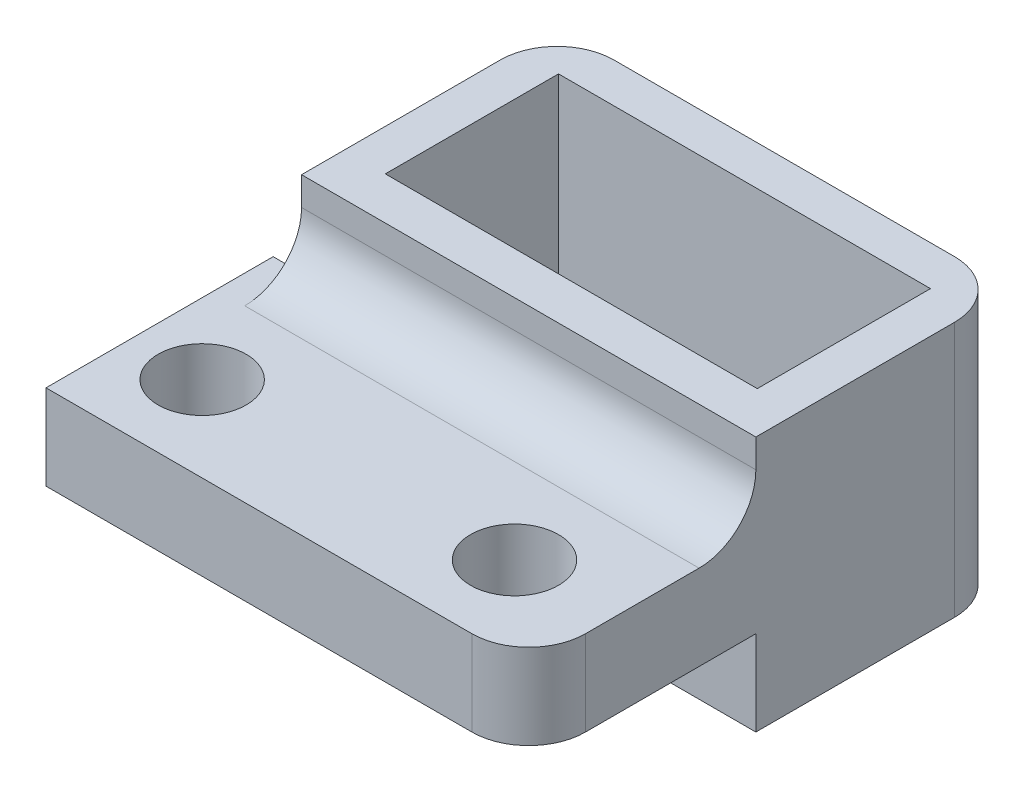
SolidWorks part; units mm, degrees
ref_plane "Alzado" through (0, 0, 0) normal (0, 0, 1) x (1, 0, 0)
ref_plane "Planta" through (0, 0, 0) normal (0, 1, 0) x (1, 0, 0)
ref_plane "Vista lateral" through (0, 0, 0) normal (1, 0, 0) x (0, 0, -1)
sketch "Croquis1" plane through (0, 0, 0) normal (0, 1, 0) x (1, 0, 0)
  line L0 (9, 18) -> (9, 0) construction
  line L1 (0, 0) -> (18, 0)
  line L2 (0, 0) -> (0, 18)
  line L3 (0, 18) -> (18, 18)
  line L4 (18, 0) -> (18, 18)
  circle A0 centre (3.5, 3) radius 1.55
  circle A1 centre (14.5, 3) radius 1.55
  dimension "D3" = 3.1
  dimension "D4" = 3
  dimension "D5" = 3.5
  dimension "D7" = 3
  dimension "D1" = 18
  dimension "D2" = 18
  dimension "D6" = 3.5
extrude "Saliente-Extruir1" add sketch "Croquis1" along normal blind 3
sketch "Croquis3" plane through (0, 3, 0) normal (0, 1, 0) x (1, 0, 0)
  line L0 (18, 0) -> (18, 18) construction
  line L1 (0, 18) -> (18, 18)
  line L2 (0, 18) -> (0, 8)
  line L3 (0, 8) -> (18, 8)
  line L4 (18, 18) -> (18, 8)
  dimension "D1" = 10
extrude "Saliente-Extruir3" add sketch "Croquis3" along normal blind 3
sketch "Croquis4" plane through (0, 0, 0) normal (0, -1, 0) x (1, 0, 0)
  line L1 (0, -18) -> (2, -18)
  line L2 (0, -18) -> (0, -8)
  line L3 (0, -8) -> (2, -8)
  line L4 (2, -18) -> (2, -8)
  dimension "D1" = 10
  dimension "D2" = 2
extrude "Cortar-Extruir1" cut sketch "Croquis4" against normal up to surface (6 mm away) up to face at (9, 6, -13)
sketch "Croquis7" plane through (0, 6, 0) normal (0, 1, 0) x (1, 0, 0)
  line L1 (3.45, 15.6) -> (16.55, 15.6)
  line L2 (3.45, 15.6) -> (3.45, 9.5)
  line L3 (3.45, 9.5) -> (16.55, 9.5)
  line L4 (16.55, 15.6) -> (16.55, 9.5)
  line L5 (2, 8) -> (18, 8) construction
  line L6 (2, 18) -> (2, 8) construction
  dimension "D1" = 6.1
  dimension "D2" = 13.1
  dimension "D3" = 1.5
  dimension "D4" = 1.45
extrude "Cortar-Extruir2" cut sketch "Croquis7" against normal up to surface (6 mm away) up to face at (6.6667, 0, -8.6667)
sketch "Croquis9" plane through (0, 0, 0) normal (0, -1, 0) x (1, 0, 0)
  line L0 (16.55, -15.6) -> (3.45, -15.6) construction
  line L1 (18, -18) -> (2, -18)
  line L2 (18, -18) -> (18, -8)
  line L3 (18, -8) -> (2, -8)
  line L4 (2, -18) -> (2, -8)
  line L5 (3.45, -15.6) -> (3.45, -9.5) construction
  line L6 (3.45, -9.5) -> (16.55, -9.5) construction
  line L7 (16.55, -9.5) -> (16.55, -15.6) construction
  line L8 (3.45, -9.5) -> (16.55, -9.5)
  line L9 (3.45, -15.6) -> (3.45, -9.5)
  line L10 (16.55, -15.6) -> (3.45, -15.6)
  line L11 (16.55, -9.5) -> (16.55, -15.6)
extrude "Saliente-Extruir4" add sketch "Croquis9" along normal blind 3
sketch "Croquis10" plane through (0, -3, 0) normal (0, -1, 0) x (1, 0, 0)
  line L0 (16.55, -15.6) -> (16.55, -9.5) construction
  line L1 (16.55, -9.5) -> (3.45, -9.5) construction
  line L2 (3.45, -9.5) -> (3.45, -15.6) construction
  line L3 (3.45, -15.6) -> (16.55, -15.6) construction
  line L4 (16.55, -15.6) -> (16.55, -9.5)
  line L5 (16.55, -9.5) -> (3.45, -9.5)
  line L6 (3.45, -9.5) -> (3.45, -15.6)
  line L7 (3.45, -15.6) -> (16.55, -15.6)
  line L8 (15.8, -14.85) -> (15.8, -10.25)
  line L9 (15.8, -10.25) -> (4.2, -10.25)
  line L10 (4.2, -10.25) -> (4.2, -14.85)
  line L11 (4.2, -14.85) -> (15.8, -14.85)
  dimension "D1" = 0.75
extrude "Saliente-Extruir6" add sketch "Croquis10" against normal blind 2.5
sketch "Croquis11" plane through (0, 6, 0) normal (0, 1, 0) x (1, 0, 0)
  line L0 (18, 8) -> (18, 18) construction
  line L1 (2, 18) -> (18, 18)
  line L2 (2, 18) -> (2, 17)
  line L3 (2, 17) -> (18, 17)
  line L4 (18, 18) -> (18, 17)
  dimension "D1" = 1
extrude "Cortar-Extruir4" cut sketch "Croquis11" against normal up to surface (9 mm away) up to face at (10, -3, -13)
fillet "Redondeo1" radius 2 3 edges at (18, 1.5, -17) (2, 1.5, -17) (18, 1.5, 0)
sketch "Croquis12" plane through (0, 0, 0) normal (-1, 0, 0) x (0, 0, 1)
  line L4 (0, 3) -> (-8, 3)
  line L5 (-8, 3) -> (-8, 0)
  line L6 (-8, 0) -> (0, 0)
  line L7 (0, 0) -> (0, 3)
  line L8 (0, 3) -> (-8, 3)
  line L9 (-8, 3) -> (-8, 0)
  line L10 (-8, 0) -> (0, 0)
  line L11 (0, 0) -> (0, 3)
  dimension "D1" = 0
extrude "Cortar-Extruir5" cut sketch "Croquis12" against normal blind 1
fillet "Redondeo2" radius 2 1 edges at (10, 3, -8)
